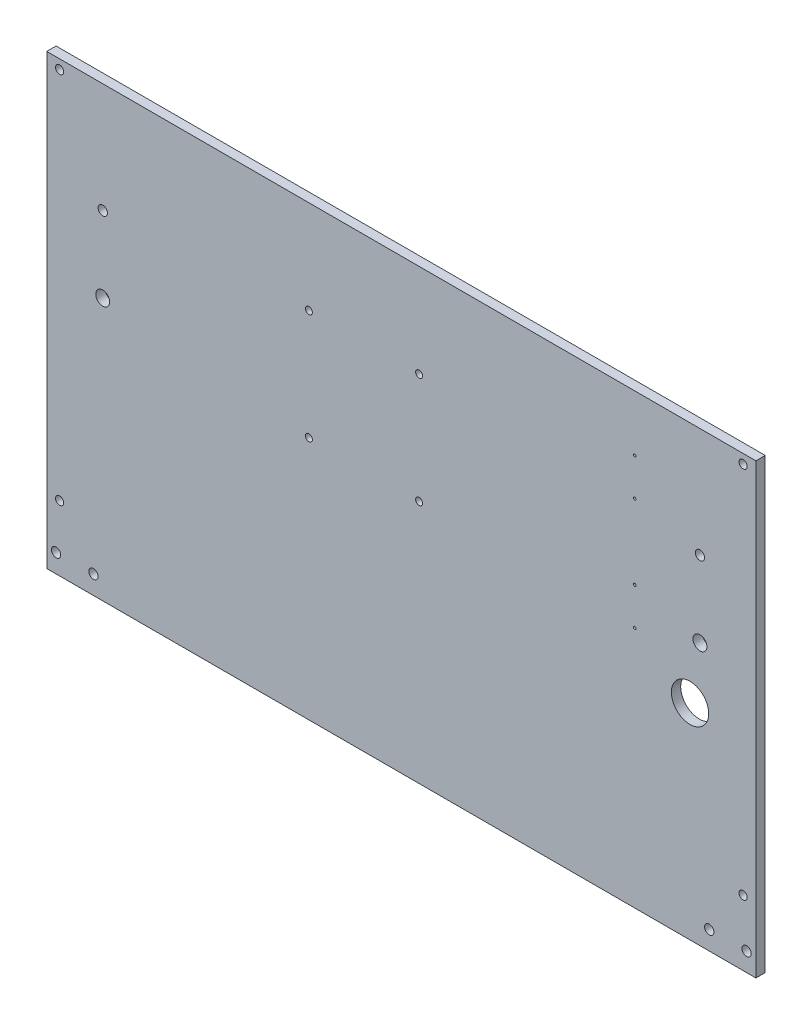
SolidWorks part; units mm, degrees
ref_plane "Front Plane" through (0, 0, 0) normal (0, 0, 1) x (1, 0, 0)
ref_plane "Top Plane" through (0, 0, 0) normal (0, 1, 0) x (1, 0, 0)
ref_plane "Right Plane" through (0, 0, 0) normal (1, 0, 0) x (0, 0, -1)
sketch "Sketch1" plane through (0, 0, 0) normal (0, 0, 1) x (1, 0, 0)
  line L1 (-241.3, -152.4) -> (241.3, -152.4)
  line L2 (-241.3, -152.4) -> (-241.3, 152.4)
  line L3 (-241.3, 152.4) -> (241.3, 152.4)
  line L4 (241.3, -152.4) -> (241.3, 152.4)
  line L5 (-241.3, -152.4) -> (241.3, 152.4) construction
  line L6 (-241.3, 152.4) -> (241.3, -152.4) construction
  point P0 (0, 0)
  dimension "D1" = 482.6
  dimension "D2" = 304.8
extrude "Boss-Extrude1" add sketch "Sketch1" along normal blind 6.35
sketch "Sketch2" plane through (0, 0, 6.35) normal (0, 0, 1) x (1, 0, 0)
  line L0 (-241.3, 0) -> (241.3, 0) construction
  line L1 (-241.3, 152.4) -> (-241.3, -152.4) construction
  line L2 (241.3, -152.4) -> (241.3, 152.4) construction
  line L3 (241.3, 152.4) -> (-241.3, 152.4) construction
  circle A0 centre (-232.5624, 146.05) radius 2.7813
  circle A1 centre (-232.5624, -107.95) radius 2.7813
  dimension "D2" = 5.5626
  dimension "D3" = 5.5626
  dimension "D1" = 8.7376
  dimension "D4" = 6.35
  dimension "D5" = 254
extrude "Cut-Extrude1" cut sketch "Sketch2" against normal through all
mirror "Mirror1" about plane through (0, 0, 0) normal (1, 0, 0) of "Cut-Extrude1"
sketch "Sketch3" plane through (0, 0, 6.35) normal (0, 0, 1) x (1, 0, 0)
  line L0 (-241.3, -139.7) -> (241.3, -139.7) construction
  line L1 (-241.3, 152.4) -> (-241.3, -152.4) construction
  line L2 (241.3, -152.4) -> (241.3, 152.4) construction
  line L3 (-241.3, -152.4) -> (241.3, -152.4) construction
  circle A0 centre (-234.95, -139.7) radius 3.175
  circle A1 centre (-209.55, -139.7) radius 3.175
  dimension "D2" = 6.35
  dimension "D3" = 6.35
  dimension "D4" = 25.4
  dimension "D5" = 6.35
  dimension "D1" = 12.7
extrude "Cut-Extrude2" cut sketch "Sketch3" against normal through all
mirror "Mirror2" about plane through (0, 0, 0) normal (1, 0, 0) of "Cut-Extrude2"
sketch "Sketch4" plane through (0, 0, 6.35) normal (0, 0, 1) x (1, 0, 0)
  line L0 (241.3, 152.4) -> (-241.3, 152.4) construction
  circle A0 centre (196.469, -12.7) radius 12.7
  dimension "D2" = 25.4
  dimension "D1" = 196.469
  dimension "D3" = 165.1
extrude "Cut-Extrude3" cut sketch "Sketch4" against normal through all
sketch "Sketch5" plane through (0, 0, 6.35) normal (0, 0, 1) x (1, 0, 0)
  line L0 (241.3, 152.4) -> (-241.3, 152.4) construction
  line L1 (-62.9, 13.9) -> (12.1, 13.9) construction
  line L2 (-62.9, 13.9) -> (-62.9, 88.9) construction
  line L3 (-62.9, 88.9) -> (12.1, 88.9) construction
  line L4 (12.1, 13.9) -> (12.1, 88.9) construction
  line L5 (-62.9, 13.9) -> (12.1, 88.9) construction
  line L6 (-62.9, 88.9) -> (12.1, 13.9) construction
  circle A0 centre (-62.9, 88.9) radius 2.3749
  circle A1 centre (12.1, 88.9) radius 2.3749
  circle A2 centre (12.1, 13.9) radius 2.3749
  circle A3 centre (-62.9, 13.9) radius 2.3749
  point P0 (-25.4, 51.4)
  dimension "D4" = 4.7498
  dimension "D5" = 4.7498
  dimension "D6" = 4.7498
  dimension "D7" = 4.7498
  dimension "D1" = 75
  dimension "D2" = 75
  dimension "D3" = 63.5
  dimension "D8" = 25.4
extrude "Cut-Extrude4" cut sketch "Sketch5" against normal through all
sketch "Sketch6" plane through (0, 0, 6.35) normal (0, 0, 1) x (1, 0, 0)
  line L0 (241.3, -152.4) -> (241.3, 152.4) construction
  line L1 (-241.3, 152.4) -> (-241.3, -152.4) construction
  circle A0 centre (-203.2, 77.7271) radius 3.175
  circle A1 centre (-203.2, 26.0961) radius 4.7625
  circle A2 centre (203.2, 77.7271) radius 3.175
  circle A3 centre (203.2, 26.0961) radius 4.7625
  dimension "D1" = 6.35
  dimension "D2" = 6.35
  dimension "D3" = 9.525
  dimension "D4" = 9.525
  dimension "D5" = 38.1
  dimension "D6" = 38.1
extrude "Cut-Extrude5" cut sketch "Sketch6" against normal through all
sketch "Sketch7" plane through (0, 0, 6.35) normal (0, 0, 1) x (1, 0, 0)
  line L0 (158.8215, 152.4) -> (158.8215, -152.4) construction
  line L1 (241.3, 152.4) -> (-241.3, 152.4) construction
  line L2 (-241.3, -152.4) -> (241.3, -152.4) construction
  circle A0 centre (158.8215, 114.3) radius 0.889
  circle A1 centre (158.8215, 88.9) radius 0.889
  circle A2 centre (158.8215, 38.1) radius 0.889
  circle A3 centre (158.8215, 12.7) radius 0.889
  dimension "D1" = 1.778
  dimension "D2" = 1.778
  dimension "D3" = 1.778
  dimension "D4" = 1.778
  dimension "D8" = 38.1
  dimension "D5" = 25.4
  dimension "D6" = 25.4
  dimension "D7" = 50.8
extrude "Cut-Extrude6" cut sketch "Sketch7" against normal through all
